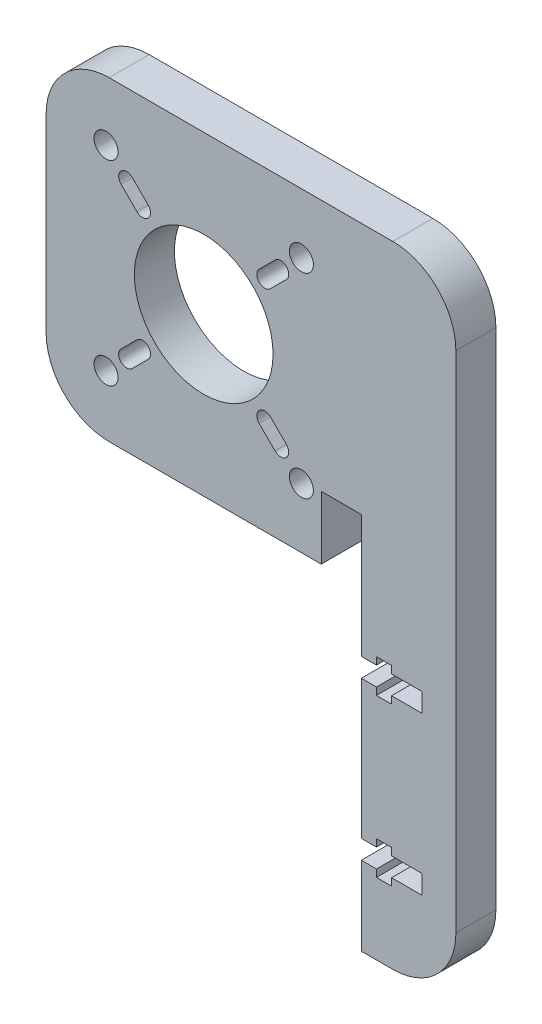
SolidWorks part; units mm, degrees
ref_plane "Front Plane" through (0, 0, 0) normal (0, 0, 1) x (1, 0, 0)
ref_plane "Top Plane" through (0, 0, 0) normal (0, 1, 0) x (1, 0, 0)
ref_plane "Right Plane" through (0, 0, 0) normal (1, 0, 0) x (0, 0, -1)
sketch "Sketch1" plane through (0, 0, 0) normal (0, 0, 1) x (1, 0, 0)
  line L0 (-12.2174, 12.2174) -> (-9.7029, 9.7029) construction
  line L1 (-11.3194, 13.1154) -> (-8.8049, 10.6009)
  line L2 (-13.1154, 11.3194) -> (-10.6009, 8.8049)
  line L3 (-11, 0) -> (11, 0) construction
  line L4 (-9.7029, 9.7029) -> (0, 0) construction
  line L5 (-15.494, 15.494) -> (-10.9972, 10.9972) construction
  line L6 (15.494, 15.494) -> (10.9972, 10.9972) construction
  line L7 (9.7029, 9.7029) -> (0, 0) construction
  line L8 (12.2174, 12.2174) -> (9.7029, 9.7029) construction
  line L9 (13.1154, 11.3194) -> (10.6009, 8.8049)
  line L10 (11.3194, 13.1154) -> (8.8049, 10.6009)
  line L11 (15.494, -15.494) -> (10.9972, -10.9972) construction
  line L12 (9.7029, -9.7029) -> (0, 0) construction
  line L13 (12.2174, -12.2174) -> (9.7029, -9.7029) construction
  line L14 (11.3194, -13.1154) -> (8.8049, -10.6009)
  line L15 (13.1154, -11.3194) -> (10.6009, -8.8049)
  line L16 (-15.494, -15.494) -> (-10.9972, -10.9972) construction
  line L17 (-9.7029, -9.7029) -> (0, 0) construction
  line L18 (-12.2174, -12.2174) -> (-9.7029, -9.7029) construction
  line L19 (-13.1154, -11.3194) -> (-10.6009, -8.8049)
  line L20 (-11.3194, -13.1154) -> (-8.8049, -10.6009)
  line L21 (25, 25) -> (40, 25)
  line L22 (-25, 25) -> (25, 25)
  line L23 (-25, 25) -> (-25, -25)
  line L24 (-25, -25) -> (25, -25)
  line L25 (25, 25) -> (25, -25)
  line L26 (40, 25) -> (40, -75)
  line L27 (40, -75) -> (25, -75)
  line L28 (25, -75) -> (25, -25)
  line L29 (25, -34.5) -> (27.4, -34.5)
  line L30 (27.4, -34.5) -> (27.4, -33.34)
  line L31 (27.4, -33.34) -> (29.8, -33.34)
  line L32 (29.8, -33.34) -> (29.8, -34.5)
  line L33 (29.8, -34.5) -> (34.65, -34.5)
  line L34 (34.65, -34.5) -> (34.65, -37.5)
  line L35 (34.65, -37.5) -> (29.8, -37.5)
  line L36 (29.8, -37.5) -> (29.8, -38.66)
  line L37 (29.8, -38.66) -> (27.4, -38.66)
  line L38 (27.4, -38.66) -> (27.4, -37.5)
  line L39 (27.4, -37.5) -> (25, -37.5)
  line L40 (18.65, -25) -> (18.65, -15)
  line L41 (18.65, -15) -> (25, -15)
  line L42 (25, -59.5) -> (27.4, -59.5)
  line L43 (27.4, -59.5) -> (27.4, -58.34)
  line L44 (27.4, -58.34) -> (29.8, -58.34)
  line L45 (29.8, -58.34) -> (29.8, -59.5)
  line L46 (29.8, -59.5) -> (34.65, -59.5)
  line L47 (34.65, -59.5) -> (34.65, -62.5)
  line L48 (34.65, -62.5) -> (29.8, -62.5)
  line L49 (29.8, -63.66) -> (27.4, -63.66)
  line L50 (29.8, -62.5) -> (29.8, -63.66)
  line L51 (27.4, -63.66) -> (27.4, -62.5)
  line L52 (27.4, -62.5) -> (25, -62.5)
  circle A0 centre (0, 0) radius 11
  arc A1 (-11.3194, 13.1154) -> (-13.1154, 11.3194) centre (-12.2174, 12.2174) ccw
  arc A2 (-10.6009, 8.8049) -> (-8.8049, 10.6009) centre (-9.7029, 9.7029) ccw
  circle A3 centre (-15.494, 15.494) radius 1.905
  circle A4 centre (15.494, 15.494) radius 1.905
  arc A5 (13.1154, 11.3194) -> (11.3194, 13.1154) centre (12.2174, 12.2174) ccw
  arc A6 (8.8049, 10.6009) -> (10.6009, 8.8049) centre (9.7029, 9.7029) ccw
  circle A7 centre (15.494, -15.494) radius 1.905
  arc A8 (11.3194, -13.1154) -> (13.1154, -11.3194) centre (12.2174, -12.2174) ccw
  arc A9 (10.6009, -8.8049) -> (8.8049, -10.6009) centre (9.7029, -9.7029) ccw
  circle A10 centre (-15.494, -15.494) radius 1.905
  arc A11 (-13.1154, -11.3194) -> (-11.3194, -13.1154) centre (-12.2174, -12.2174) ccw
  arc A12 (-8.8049, -10.6009) -> (-10.6009, -8.8049) centre (-9.7029, -9.7029) ccw
  point P5 (-10.9602, 10.9602)
  point P21 (10.9602, 10.9602)
  point P32 (10.9602, -10.9602)
  point P43 (-10.9602, -10.9602)
  point P52 (0, 0)
  point P78 (34.65, -36)
  dimension "D1" = 22
  dimension "D3" = 1.27
  dimension "D6" = 3.81
  dimension "D2" = 1.778
  dimension "D4" = 45
  dimension "D5" = 15.5
  dimension "D7" = 15.494
  dimension "D9" = 25
  dimension "D10" = 50
  dimension "D11" = 25
  dimension "D12" = 50
  dimension "D13" = 3
  dimension "D14" = 9.65
  dimension "D15" = 5.32
  dimension "D16" = 2.4
  dimension "D17" = 2.66
  dimension "D18" = 2.4
  dimension "D19" = 15
  dimension "D20" = 100
  dimension "D21" = 37.5
  dimension "D22" = 6.35
  dimension "D23" = 10
  dimension "D24" = 2
  dimension "D8" = 4
extrude "Boss-Extrude1" add sketch "Sketch1" along normal blind 6.35 contours L25 L22 L23 L24 A12 L20 A11 L19 A10 A9 L15 A8 L14 A7 A6 L10 A5 L9 A4 A3 A2 L2 A1 L1 A0 | L38 L39 L28 L27 L26 L21 L25 L29 L30 L31 L32 L33 L34 L35 L36 L37 | L24 region at (24.2929, 5, 0) region at (32.6386, -23.8663, 0)
fillet "Fillet1" radius 10 4 edges at (40, -75, 3.175) (40, 25, 3.175) (-25, -25, 3.175) (-25, 25, 3.175)
